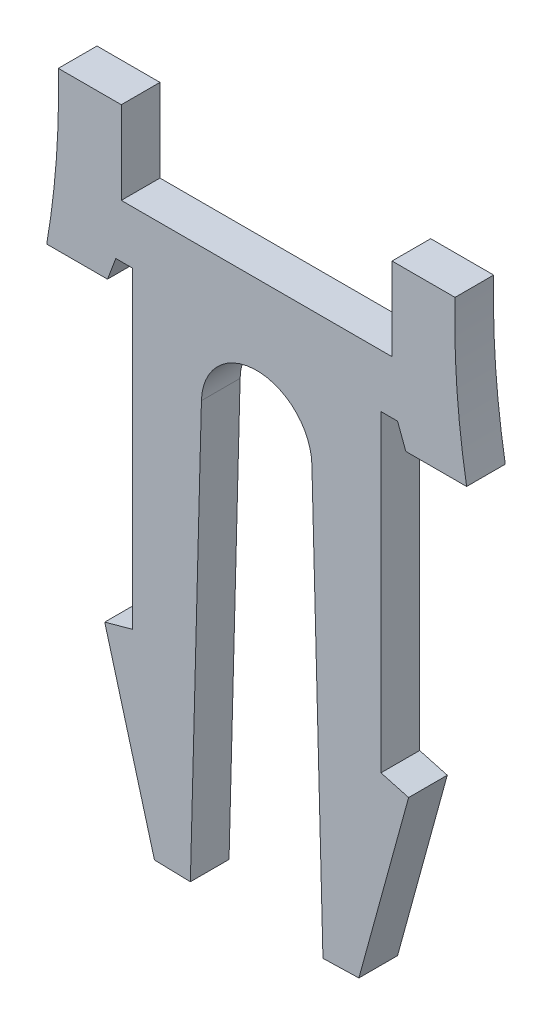
SolidWorks part; units mm, degrees
material "AISI 1020 Steel, Cold Rolled"
ref_plane "Front" through (0, 0, 0) normal (0, 0, 1) x (1, 0, 0)
ref_plane "Top" through (0, 0, 0) normal (0, 1, 0) x (1, 0, 0)
ref_plane "Right" through (0, 0, 0) normal (1, 0, 0) x (0, 0, -1)
sketch "Sketch1" plane through (0, 0, 0) normal (0, 0, 1) x (1, 0, 0)
  line L0 (0, 0) -> (0, -3.8079) construction
  line L1 (-0.4998, 0.0131) -> (-0.6, -3.8079)
  line L2 (0.4998, 0.0131) -> (0.6, -3.8079)
  line L3 (-0.6, -3.8079) -> (0.6, -3.8079) construction
  line L4 (0.6, -3.8079) -> (0.925, -3.7994)
  line L5 (-0.6, -3.8079) -> (-0.925, -3.7994)
  line L6 (-1.225, 1.22) -> (1.225, 1.22)
  line L7 (0, 0) -> (0, 1.22) construction
  line L8 (0.925, -3.7994) -> (1.375, -2.16)
  line L9 (-0.925, -3.7994) -> (-1.375, -2.16)
  line L10 (1.375, -2.16) -> (1.125, -2.0914)
  line L11 (-1.375, -2.16) -> (-1.125, -2.0914)
  line L12 (-1.125, -2.0914) -> (-1.125, 0.74)
  line L13 (-1.225, 1.22) -> (-1.225, 1.97)
  line L14 (-1.225, 1.97) -> (-1.795, 1.97)
  line L15 (-1.225, 1.22) -> (-1.815, 1.22) construction
  line L16 (1.225, 1.22) -> (1.815, 1.22) construction
  line L17 (-1.9, 0.54) -> (1.9, 0.54) construction
  line L18 (1.225, 1.22) -> (1.225, 1.97)
  line L19 (1.225, 1.97) -> (1.795, 1.97)
  line L20 (-1.9, 0.54) -> (-1.35, 0.54)
  line L21 (-1.35, 0.54) -> (-1.275, 0.74)
  line L22 (-1.275, 0.74) -> (-1.125, 0.74)
  line L23 (1.9, 0.54) -> (1.35, 0.54)
  line L24 (1.35, 0.54) -> (1.275, 0.74)
  line L25 (1.275, 0.74) -> (1.125, 0.74)
  line L26 (1.125, 0.74) -> (1.125, -2.0914)
  arc A0 (0.4998, 0.0131) -> (-0.4998, 0.0131) centre (0, 0) ccw
  arc A1 (-1.795, 1.97) -> (-1.9, 0.54) centre (-9.1429, 1.7907) cw
  arc A2 (1.795, 1.97) -> (1.9, 0.54) centre (9.1429, 1.7907) ccw
  dimension "D1" = 1
  dimension "D2" = 1.2
  dimension "D4" = 0.72
  dimension "D5" = 2.7
  dimension "D6" = 2.45
  dimension "D7" = 2.75
  dimension "D8" = 1.7
  dimension "D9" = 2.25
  dimension "D10" = 2.9
  dimension "D11" = 1.85
  dimension "D12" = 0.75
  dimension "D13" = 0.57
  dimension "D14" = 3.63
  dimension "D15" = 3.8
  dimension "D16" = 1.43
  dimension "D17" = 0.55
  dimension "D18" = 2.55
  dimension "D19" = 5.0194
base flange "Base-Flange1" sketch "Sketch1" thickness 0.35 reverse thickness direction no parameters "D1"=1.27
sketch "Bend-Lines1" plane through (0, 0, 0) normal (0, 1, 0) x (1, 0, 0)
sketch "Bounding-Box1" plane through (0, 0, 0) normal (0, 1, 0) x (1, 0, 0)
sheet metal parameters "Sheet-Metal(1)" thickness 0.35 parameters "D1"=1.27
flat pattern "Flat-Pattern(1)" [suppressed]
sketch "Bend-Lines2" plane through (0, 0, 0) normal (0, 1, 0) x (1, 0, 0)
sketch "Bounding-Box2" [suppressed] plane through (0, 0, 0) normal (0, 1, 0) x (1, 0, 0)
